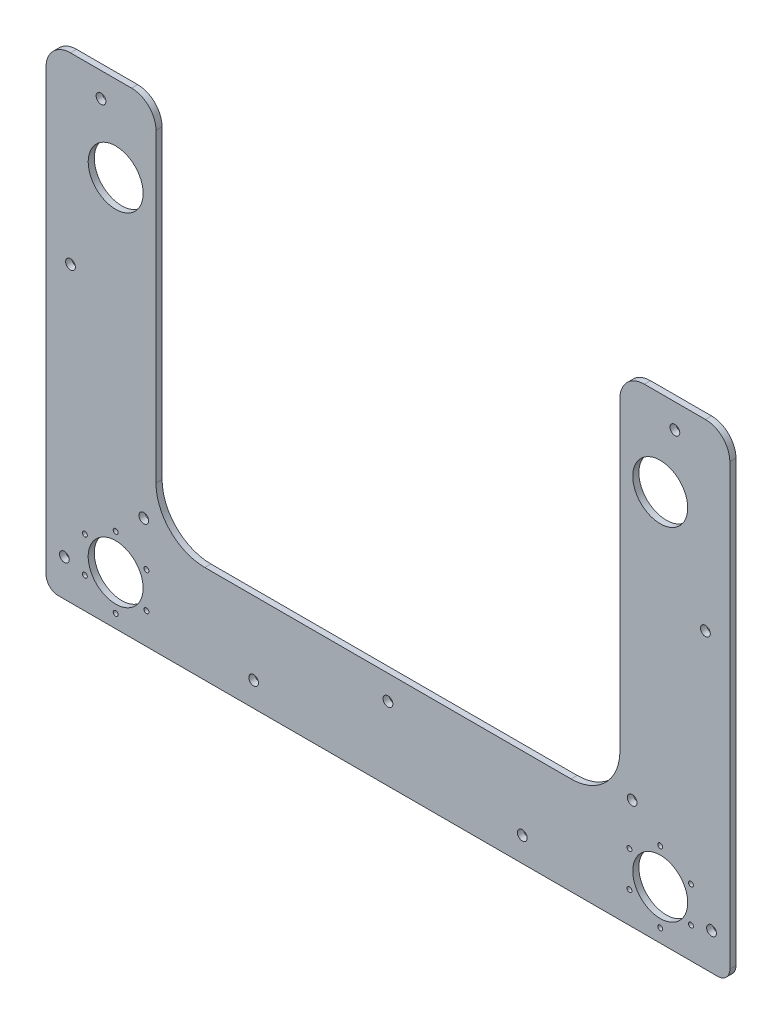
SolidWorks part; units mm, degrees
ref_plane "Front Plane" through (0, 0, 0) normal (0, 0, 1) x (1, 0, 0)
ref_plane "Top Plane" through (0, 0, 0) normal (0, 1, 0) x (1, 0, 0)
ref_plane "Right Plane" through (0, 0, 0) normal (1, 0, 0) x (0, 0, -1)
sketch "Sketch1" plane through (0, 0, 0) normal (0, 0, 1) x (1, 0, 0)
  line L5 (120.65, -152.4) -> (120.65, -6.35)
  line L6 (127, 0) -> (171.45, 0) construction
  line L7 (177.8, -6.35) -> (177.8, -222.25)
  line L10 (0, -206.2199) -> (0, -63.6275) construction
  line L11 (-54.9244, 0) -> (300.6756, 0) construction
  line L13 (12.7, -177.8) -> (95.25, -177.8)
  line L14 (12.7, -228.6) -> (171.45, -228.6)
  line L15 (141.605, -25.4) -> (141.605, -84.2822) construction
  line L16 (141.605, -25.4) -> (141.605, -127) construction
  line L17 (-141.605, -25.4) -> (-141.605, -203.2) construction
  line L18 (-141.605, -25.4) -> (-141.605, -127) construction
  line L19 (-141.605, -19.05) -> (-141.605, -77.9322) construction
  line L20 (141.605, -25.4) -> (141.605, -203.2) construction
  line L22 (-120.65, -152.4) -> (-120.65, -6.35)
  line L23 (-12.7, -177.8) -> (-95.25, -177.8)
  line L24 (-12.7, -228.6) -> (-171.45, -228.6)
  line L25 (-177.8, -6.35) -> (-177.8, -222.25)
  line L26 (-12.7, -177.8) -> (12.7, -177.8)
  line L27 (-12.7, -228.6) -> (12.7, -228.6)
  line L28 (-177.8, -6.35) -> (-177.8, 6.35)
  line L29 (-165.1, 19.05) -> (-133.35, 19.05)
  line L30 (-120.65, 6.35) -> (-120.65, -6.35)
  line L31 (120.65, 6.35) -> (120.65, -6.35)
  line L32 (177.8, -6.35) -> (177.8, 6.35)
  line L33 (165.1, 19.05) -> (133.35, 19.05)
  arc A0 (95.25, -177.8) -> (120.65, -152.4) centre (95.25, -152.4) ccw
  arc A4 (120.65, -6.35) -> (127, 0) centre (127, -6.35) cw construction
  circle A8 centre (141.605, -25.4) radius 14.2875
  circle A9 centre (141.605, -25.4) radius 38.1 construction
  arc A10 (177.8, -6.35) -> (171.45, 0) centre (171.45, -6.35) ccw construction
  arc A11 (171.45, -228.6) -> (177.8, -222.25) centre (171.45, -222.25) ccw
  arc A14 (141.605, -82.55) -> (120.9214, -78.6758) centre (141.605, -25.4) ccw construction
  arc A15 (-141.605, -82.55) -> (-120.9214, -78.6758) centre (-141.605, -25.4) cw construction
  circle A16 centre (-141.605, -25.4) radius 38.1 construction
  circle A17 centre (-141.605, -25.4) radius 14.2875
  arc A19 (-95.25, -177.8) -> (-120.65, -152.4) centre (-95.25, -152.4) cw
  circle A20 centre (141.605, -127) radius 38.1 construction
  circle A21 centre (-141.605, -127) radius 38.1 construction
  arc A23 (-171.45, -228.6) -> (-177.8, -222.25) centre (-171.45, -222.25) cw
  circle A24 centre (-141.605, -203.2) radius 14.2875
  circle A25 centre (-141.605, -184.7225) radius 1.27
  circle A26 centre (-125.603, -193.9612) radius 1.27
  circle A27 centre (-125.603, -212.4388) radius 1.27
  circle A28 centre (-141.605, -221.6775) radius 1.27
  circle A29 centre (-157.607, -212.4388) radius 1.27
  circle A30 centre (-157.607, -193.9612) radius 1.27
  circle A31 centre (157.607, -212.4388) radius 1.27
  circle A32 centre (157.607, -193.9612) radius 1.27
  circle A33 centre (141.605, -184.7225) radius 1.27
  circle A34 centre (125.603, -193.9612) radius 1.27
  circle A35 centre (125.603, -212.4388) radius 1.27
  circle A36 centre (141.605, -221.6775) radius 1.27
  circle A37 centre (141.605, -203.2) radius 14.2875
  circle A39 centre (-69.85, -215.9) radius 2.54
  circle A40 centre (69.85, -215.9) radius 2.54
  circle A42 centre (0, -190.5) radius 2.54
  circle A43 centre (-127, -171.45) radius 2.54
  arc A44 (-133.35, 19.05) -> (-120.65, 6.35) centre (-133.35, 6.35) cw
  arc A45 (-177.8, 6.35) -> (-165.1, 19.05) centre (-165.1, 6.35) cw
  arc A46 (133.35, 19.05) -> (120.65, 6.35) centre (133.35, 6.35) ccw
  arc A47 (177.8, 6.35) -> (165.1, 19.05) centre (165.1, 6.35) ccw
  circle A50 centre (-149.225, 6.35) radius 2.54
  circle A51 centre (127, -171.45) radius 2.54
  circle A53 centre (149.225, 6.35) radius 2.54
  circle A54 centre (-168.275, -209.55) radius 2.54
  circle A56 centre (168.275, -209.55) radius 2.54
  circle A58 centre (-165.1, -76.2) radius 2.54
  circle A59 centre (165.1, -76.2) radius 2.54
  point P2 (177.8, -44.45)
  point P18 (177.8, 0)
  point P23 (177.8, -228.6)
  point P24 (177.8, -228.6)
  point P31 (177.8, 0)
  point P48 (-177.8, 0)
  point P49 (-177.8, -228.6)
  point P51 (-177.8, -44.45)
  point P78 (-141.605, -203.2)
  point P118 (0, 0)
  point P119 (0, 0)
  point P120 (0, 0)
  point P121 (0, 0)
  point P122 (-168.275, -146.05)
  point P123 (0, 0)
  point P124 (-123.5946, -165.1)
  point P125 (0, 0)
  point P126 (165.1, -76.2)
  point P127 (-165.1, -78.6758)
  point P128 (-165.1, -74.7211)
  point P129 (-165.1, -74.9398)
  dimension "D6" = 25.4
  dimension "D7" = 6.35
  dimension "D8" = 6.35
  dimension "D9" = 177.8
  dimension "D10" = 28.575
  dimension "D12" = 76.2
  dimension "D13" = 57.15
  dimension "D15" = 28.575
  dimension "D18" = 76.2
  dimension "D21" = 2.54
  dimension "D29" = 9.525
  dimension "D32" = 5.08
  dimension "D35" = 5.08
  dimension "D37" = 5.08
  dimension "D40" = 12.7
  dimension "D43" = 5.08
  dimension "D45" = 12.7
  dimension "D30" = 5.08
  dimension "D41" = 5.08
  dimension "D2" = 120.65
  dimension "D3" = 177.8
  dimension "D4" = 228.6
  dimension "D5" = 177.8
  dimension "D11" = 20.955
  dimension "`" = 25.4
  dimension "D14" = 57.15
  dimension "D16" = 184.15
  dimension "D17" = 101.6
  dimension "D19" = 25.4
  dimension "D20" = 107.95
  dimension "D22" = 0
  dimension "D23" = 18.4775
  dimension "D25" = 6.9225
  dimension "D26" = 19.05
  dimension "D27" = 25.4
  dimension "D28" = 25.4
  dimension "D31" = 95.25
  dimension "D33" = 12.7
  dimension "D34" = 12.7
  dimension "D36" = 12.7
  dimension "D38" = 57.15
  dimension "D39" = 19.05
  dimension "D42" = 6.35
  dimension "D44" = 28.575
  dimension "D24" = 6
extrude "Boss-Extrude3" add sketch "Sketch1" along normal blind 3.175
